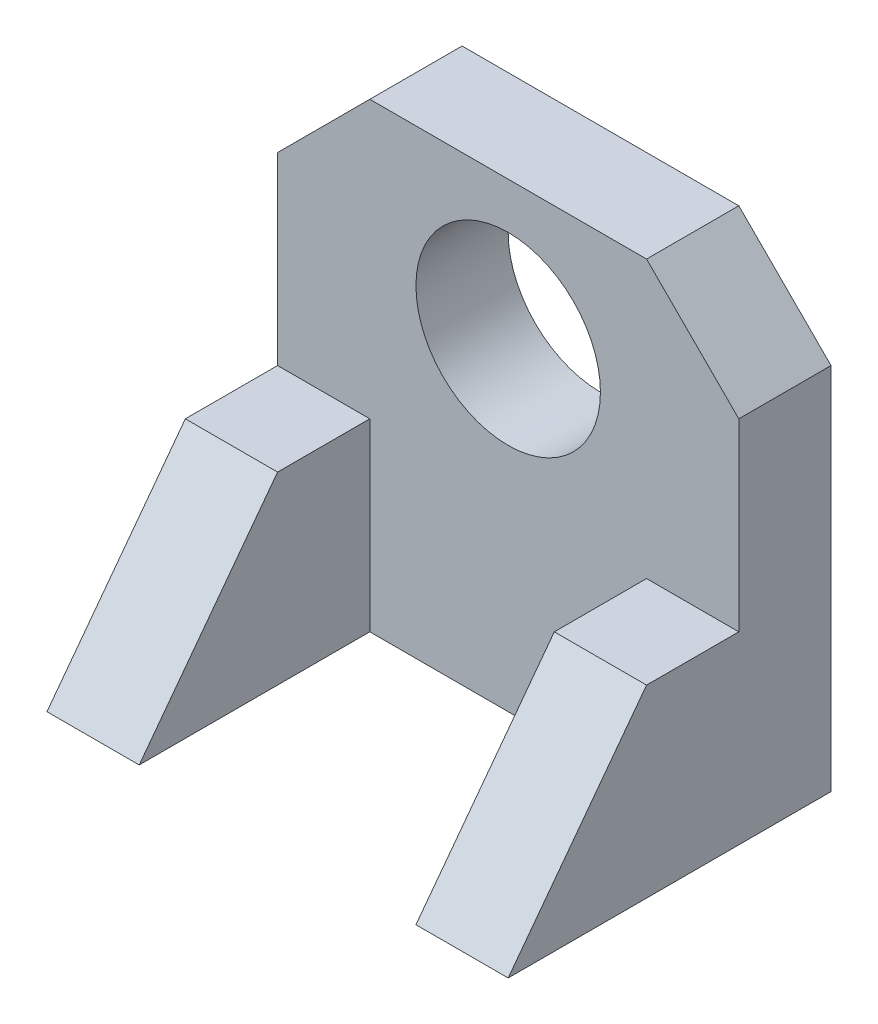
SolidWorks part; units mm, degrees
ref_plane "Front Plane" through (0, 0, 0) normal (0, 0, 1) x (1, 0, 0)
ref_plane "Top Plane" through (0, 0, 0) normal (0, 1, 0) x (1, 0, 0)
ref_plane "Right Plane" through (0, 0, 0) normal (1, 0, 0) x (0, 0, -1)
sketch "Sketch2" plane through (0, 0, 0) normal (0, 0, 1) x (1, 0, 0)
  line L0 (-25, 0) -> (25, 0)
  line L1 (25, 0) -> (25, 50)
  line L2 (25, 50) -> (-25, 50)
  line L3 (-25, 50) -> (-25, 0)
  line L4 (15, 0) -> (15, 20)
  line L5 (15, 20) -> (25, 20)
  line L6 (-15, 0) -> (-15, 20)
  line L7 (-15, 20) -> (-25, 20)
  circle A0 centre (0, 35) radius 10
  point P4 (0, 0)
  dimension "D5" = 20
  dimension "D6" = 5
  dimension "D1" = 50
  dimension "D2" = 50
  dimension "D3" = 20
  dimension "D4" = 10
extrude "Boss-Extrude1" add sketch "Sketch2" along normal blind 10 contours L7 L6 L0 L4 L5 L1 L2 L3 A0 | L6 L7 L3 L0 | L5 L4 L0 L1 region at (-20, 10, 0) region at (-14.2929, 10, 0) region at (20, 10, 0)
extrude "Boss-Extrude3" add sketch "Sketch2<4>" along normal blind 35 contours L5 L4 L0 L1 | L6 L7 L3 L0 region at (-20, 10, 0) region at (20, 10, 0)
sketch "Sketch2<4>" plane through (0, 0, 0) normal (0, 0, 1) x (1, 0, 0) same geometry as "Sketch2"
chamfer "Chamfer8" distance 15 distance2 20 1 edges at (-20, 20, 35) first distance on face at (-20, 20, 22.5)
chamfer "Chamfer10" distance 20 distance2 15 1 edges at (20, 20, 35) first distance on face at (20, 10, 35)
chamfer "Chamfer11" distance 10 2 edges at (25, 50, 5) (-25, 50, 5)
